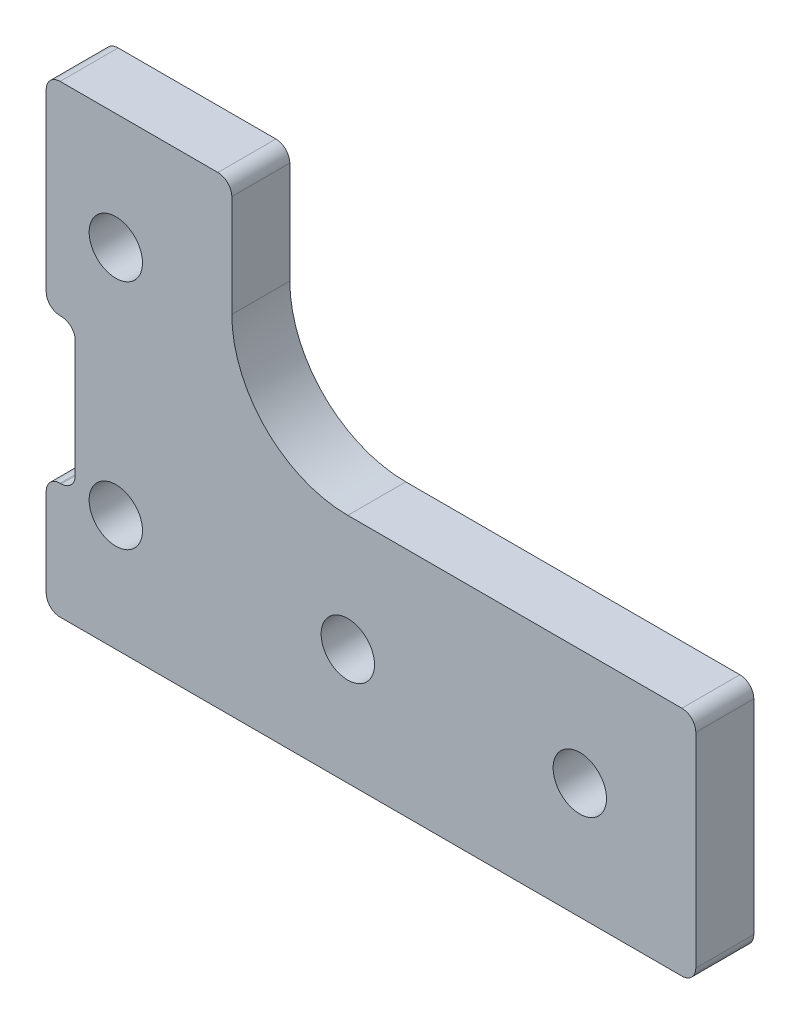
SolidWorks part; units mm, degrees
ref_plane "Front Plane" through (0, 0, 0) normal (0, 0, 1) x (1, 0, 0)
ref_plane "Top Plane" through (0, 0, 0) normal (0, 1, 0) x (1, 0, 0)
ref_plane "Right Plane" through (0, 0, 0) normal (1, 0, 0) x (0, 0, -1)
sketch "Sketch1" plane through (0, 0, 0) normal (0, 0, 1) x (1, 0, 0)
  line L0 (0, 0) -> (0, 50.8)
  line L1 (0, 50.8) -> (25.4, 50.8)
  line L2 (25.4, 50.8) -> (25.4, 25.4)
  line L3 (25.4, 25.4) -> (76.2, 25.4)
  line L4 (76.2, 25.4) -> (76.2, 0)
  line L5 (76.2, 0) -> (0, 0)
  dimension "D1" = 50.8
  dimension "D2" = 25.4
  dimension "3" = 76.2
extrude "Boss-Extrude1" add sketch "Sketch1" along normal blind 6.35
sketch "Sketch2" plane through (0, 0, 6.35) normal (0, 0, 1) x (1, 0, 0)
  line L0 (25.4, 50.8) -> (0, 50.8) construction
  line L1 (25.4, 25.4) -> (25.4, 50.8) construction
  line L2 (0, 0) -> (76.2, 0) construction
  circle A0 centre (12.7, 38.1) radius 2.921
  circle A1 centre (12.7, 12.7) radius 2.921
  circle A2 centre (38.1, 12.7) radius 2.921
  circle A3 centre (63.5, 12.7) radius 2.921
  dimension "D1" = 5.842
  dimension "D2" = 12.7
  dimension "D3" = 12.7
  dimension "D4" = 12.7
  dimension "D5" = 3
extrude "Cut-Extrude1" cut sketch "Sketch2" against normal through all
sketch "Sketch3" plane through (0, 0, 6.35) normal (0, 0, 1) x (1, 0, 0)
  line L0 (25.4, 50.8) -> (0, 50.8) construction
  line L1 (0, 0) -> (5.08, 0)
  line L2 (0, 0) -> (0, 50.8)
  line L3 (0, 50.8) -> (5.08, 50.8)
  line L4 (5.08, 0) -> (5.08, 50.8)
  dimension "D1" = 5.08
extrude "Cut-Extrude2" cut sketch "Sketch3" against normal through all
fillet "Fillet1" radius 12.7 1 edges at (25.4, 25.4, 3.175)
sketch "Sketch4" plane through (0, 0, 6.35) normal (0, 0, 1) x (1, 0, 0)
  line L0 (5.08, 0) -> (5.08, 50.8) construction
  line L1 (5.08, 28.575) -> (8.255, 28.575)
  line L2 (5.08, 28.575) -> (5.08, 12.7)
  line L3 (5.08, 12.7) -> (8.255, 12.7)
  line L4 (8.255, 28.575) -> (8.255, 12.7)
  dimension "D1" = 3.175
  dimension "D2" = 15.875
  dimension "D3" = 22.225
extrude "Cut-Extrude3" cut sketch "Sketch4" against normal through all
fillet "Fillet2" radius 1.524 9 edges at (8.255, 12.7, 3.175) (5.08, 12.7, 3.175) (8.255, 28.575, 3.175) (5.08, 28.575, 3.175) (76.2, 0, 3.175) (76.2, 25.4, 3.175) (5.08, 0, 3.175) (25.4, 50.8, 3.175) (5.08, 50.8, 3.175)
